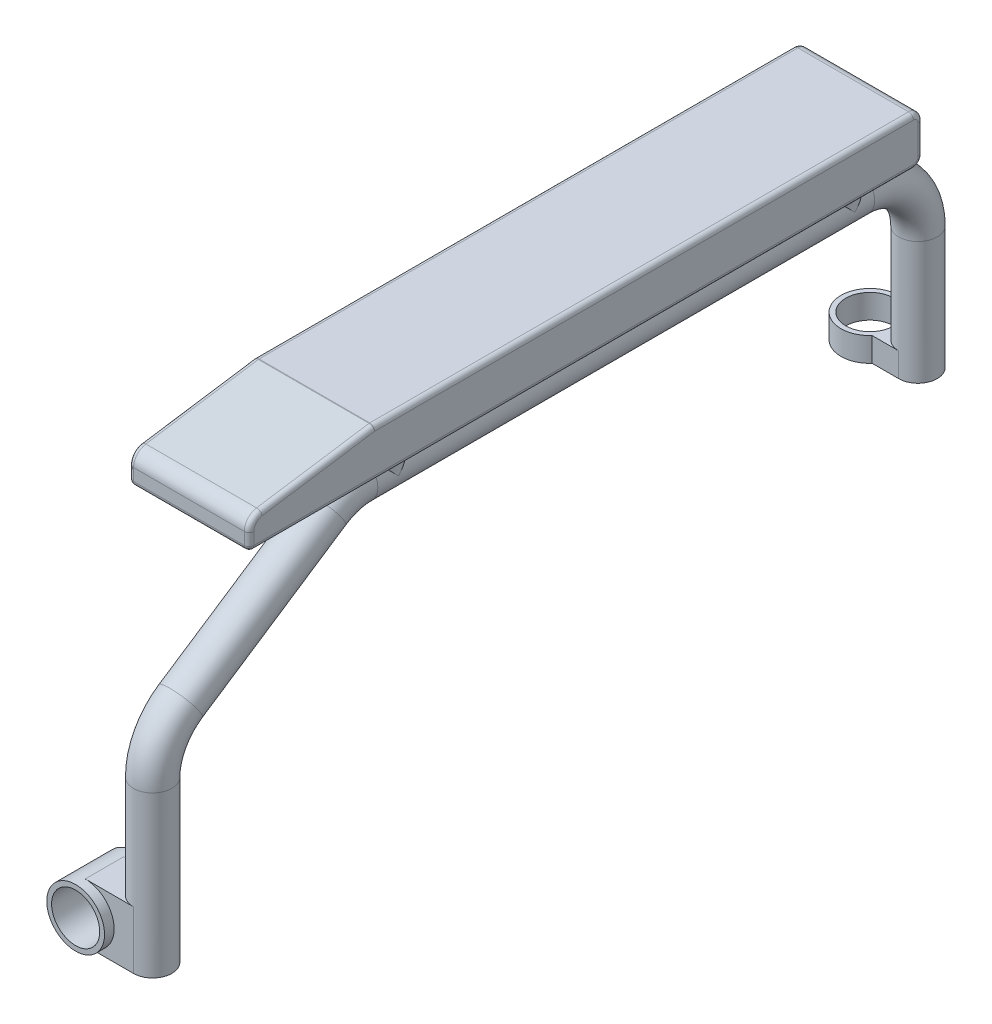
SolidWorks part; units mm, degrees
ref_plane "Front Plane" through (0, 0, 0) normal (0, 0, 1) x (1, 0, 0)
ref_plane "Top Plane" through (0, 0, 0) normal (0, 1, 0) x (1, 0, 0)
ref_plane "Right Plane" through (0, 0, 0) normal (1, 0, 0) x (0, 0, -1)
sketch "Sketch1" plane through (0, 0, 0) normal (1, 0, 0) x (0, 0, -1)
  line L0 (0, 0) -> (342.9, 0) construction
  line L1 (342.9, 0) -> (342.9, 54.61) construction
  line L2 (0, 0) -> (0, 69.3262)
  line L3 (108.6557, 152.4) -> (370.84, 152.4)
  line L4 (403.86, 119.38) -> (403.86, 54.61)
  line L5 (98.7191, 183.1531) -> (98.7191, 100.5217) construction
  line L6 (-22.3454, 87.0701) -> (49.3966, 87.0701) construction
  line L7 (14.7972, 96.8625) -> (90.4328, 146.9163)
  arc A0 (403.86, 119.38) -> (370.84, 152.4) centre (370.84, 119.38) ccw
  arc A1 (108.6557, 152.4) -> (90.4328, 146.9163) centre (108.6557, 119.38) ccw
  arc A2 (0, 69.3262) -> (14.7972, 96.8625) centre (33.02, 69.3262) cw
  point P16 (98.7191, 152.4)
  point P19 (0, 87.0701)
  dimension "D1" = 33.02
  dimension "D2" = 33.02
sketch "Sketch2" plane through (0, 0, 0) normal (0, 1, 0) x (1, 0, 0)
  circle A0 centre (0, 0) radius 10.16
sweep "Sweep1" add profiles "Sketch2" path "Sketch1"
sketch "Sketch3" plane through (0, 0, 0) normal (0, -1, 0) x (1, 0, 0)
  line L0 (0, 0) -> (-25.4, 0)
  line L1 (0, -403.86) -> (-25.4, -403.86)
sketch "Sketch4" plane through (0, 0, 0) normal (0, 0, 1) x (1, 0, 0)
  line L0 (0, 0) -> (-25.4, 0) construction
  circle A0 centre (-25.4, 0) radius 15.24
extrude "Boss-Extrude1" add sketch "Sketch4" along normal blind 15.24 and the other way blind 15.24 separate body
sketch "Sketch5" plane through (0, 0, 0) normal (0, -1, 0) x (1, 0, 0)
  circle A1 centre (0, 0) radius 10.16
  circle A2 centre (0, 0) radius 10.16
  dimension "D1" = 0
extrude "Boss-Extrude2" add sketch "Sketch5" along normal blind 15.24
sketch "Sketch6" plane through (0, 0, 0) normal (1, 0, 0) x (0, 0, -1)
  line L0 (-10.16, -15.24) -> (-10.16, 15.24)
  line L1 (15.24, 15.24) -> (-15.24, 15.24) construction
  line L2 (-10.16, 69.3262) -> (-10.16, -15.24) construction
  line L3 (-10.16, 15.24) -> (10.16, 15.24)
  line L4 (10.16, 15.24) -> (10.16, -15.24)
  line L5 (-10.16, -15.24) -> (10.16, -15.24) construction
  line L6 (10.16, -15.24) -> (-10.16, -15.24)
extrude "Boss-Extrude3" add sketch "Sketch6" against normal blind 25.4
sketch "Sketch7" plane through (0, 0, 15.24) normal (0, 0, 1) x (1, 0, 0)
  circle A0 centre (-25.4, 0) radius 12.7
extrude "Cut-Extrude1" cut sketch "Sketch7" against normal through all
ref_plane "Plane1" through (0, 54.61, 0) normal (0, 1, 0) x (1, 0, 0)
sketch "Sketch8" plane through (0, 54.61, 0) normal (0, 1, 0) x (1, 0, 0)
  circle A0 centre (-25.4, 403.86) radius 15.24
extrude "Boss-Extrude4" add sketch "Sketch8" along normal blind 12.7 separate body
sketch "Sketch10" plane through (0, 0, 0) normal (1, 0, 0) x (0, 0, -1)
  line L0 (393.7, 54.61) -> (414.02, 54.61)
  line L1 (414.02, 54.61) -> (414.02, 67.31)
  line L2 (414.02, 54.61) -> (414.02, 119.38) construction
  line L3 (414.02, 67.31) -> (393.7, 67.31)
  line L4 (393.7, 119.38) -> (393.7, 54.61) construction
  line L5 (393.7, 67.31) -> (393.7, 54.61)
extrude "Boss-Extrude5" add sketch "Sketch10" against normal blind 25.4
sketch "Sketch11" plane through (0, 67.31, 0) normal (0, 1, 0) x (1, 0, 0)
  circle A0 centre (-25.4, 403.86) radius 12.7
extrude "Cut-Extrude2" cut sketch "Sketch11" against normal blind 25.4
ref_plane "Plane2" through (0, 152.4, 0) normal (0, 1, 0) x (1, 0, 0)
sketch "Sketch12" plane through (0, 152.4, 0) normal (0, 1, 0) x (1, 0, 0)
  line L0 (0, 370.84) -> (0, 108.6557) construction
  line L1 (10.16, 370.84) -> (-10.16, 370.84) construction
  line L2 (10.16, 108.6557) -> (-10.16, 108.6557) construction
  circle A0 centre (0, 360.4101) radius 10.16
  circle A1 centre (0, 119.554) radius 10.16
extrude "Boss-Extrude6" add sketch "Sketch12" along normal blind 25.4
sketch "Sketch13" plane through (0, 0, 0) normal (1, 0, 0) x (0, 0, -1)
  line L0 (369.6857, 177.8) -> (21.68, 177.8)
  line L1 (374.7657, 182.88) -> (374.7657, 198.12)
  line L2 (369.6857, 203.2) -> (85.1707, 203.2)
  line L3 (19.14, 180.34) -> (19.14, 186.6826)
  line L4 (25.6234, 194.2174) -> (85.1707, 203.2)
  arc A0 (19.14, 186.6826) -> (25.6234, 194.2174) centre (26.76, 186.6826) cw
  arc A4 (19.14, 180.34) -> (21.68, 177.8) centre (21.68, 180.34) ccw
  arc A5 (374.7657, 182.88) -> (369.6857, 177.8) centre (369.6857, 182.88) cw
  arc A6 (374.7657, 198.12) -> (369.6857, 203.2) centre (369.6857, 198.12) ccw
  dimension "D1" = 7.62
  dimension "D5" = 2.54
  dimension "D6" = 5.08
extrude "Boss-Extrude7" add sketch "Sketch13" along normal blind 31.75 and the other way blind 31.75
fillet "Fillet1" radius 2.54 18 edges at (-31.75, 198.7087, -55.397) (-31.75, 191.6527, -20.984) (-31.75, 183.5113, -19.14) (-31.75, 178.5439, -19.8839) (-31.75, 177.8, -195.6829) (-31.75, 179.2879, -373.2778) (-31.75, 190.5, -374.7657) (-31.75, 201.7121, -373.2778) (31.75, 198.7087, -55.397) (31.75, 191.6527, -20.984) (31.75, 183.5113, -19.14) (31.75, 178.5439, -19.8839) (31.75, 177.8, -195.6829) (31.75, 179.2879, -373.2778) (31.75, 190.5, -374.7657) (31.75, 201.7121, -373.2778) (-31.75, 203.2, -227.4282) (31.75, 203.2, -227.4282)
fillet "Fillet2" radius 2.54 3 edges at (-31.0061, 202.4561, -85.2265) (31.0061, 202.4561, -85.2265) (0, 203.2, -85.1707)
